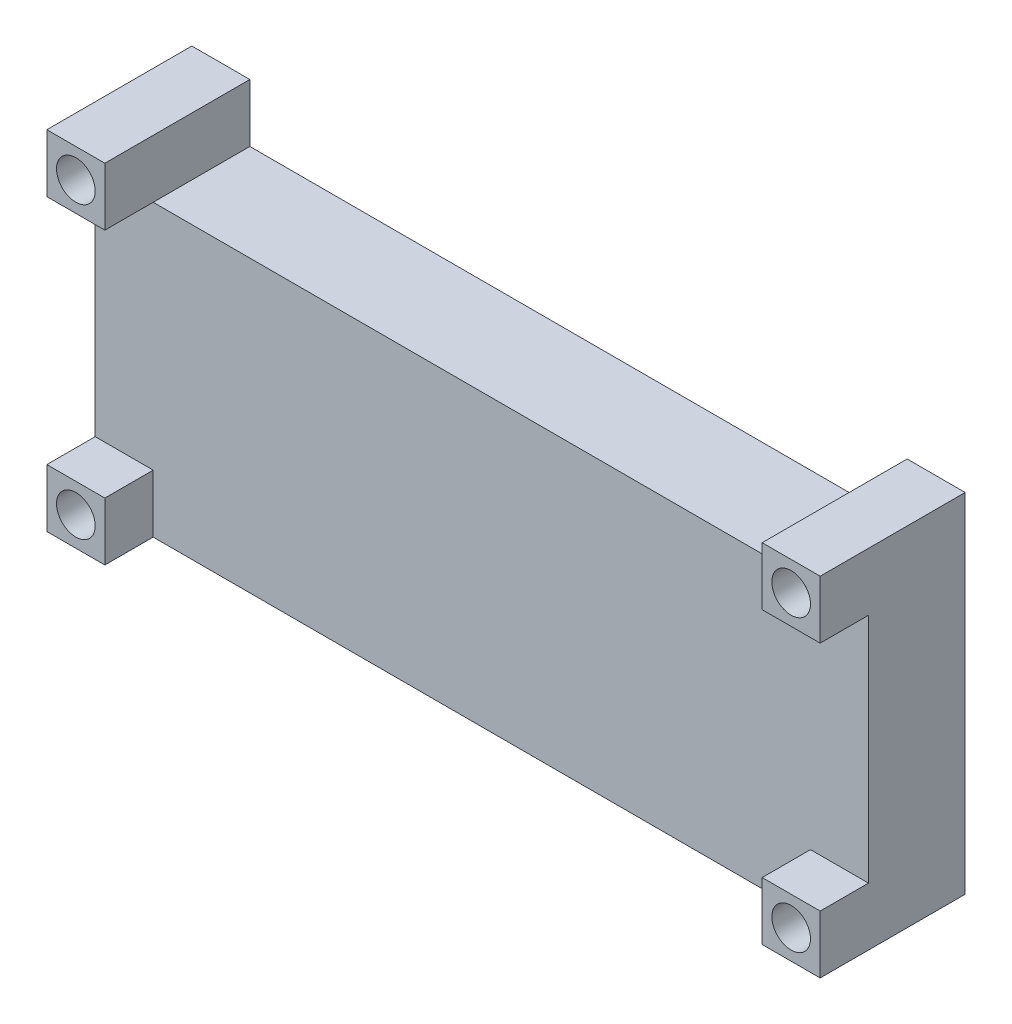
SolidWorks part; units mm, degrees
ref_plane "Front Plane" through (0, 0, 0) normal (0, 0, 1) x (1, 0, 0)
ref_plane "Top Plane" through (0, 0, 0) normal (0, 1, 0) x (1, 0, 0)
ref_plane "Right Plane" through (0, 0, 0) normal (1, 0, 0) x (0, 0, -1)
sketch "Sketch1" plane through (0, 0, 0) normal (0, 0, 1) x (1, 0, 0)
  line L0 (0, 36) -> (6, 36)
  line L1 (0, 0) -> (80, 0)
  line L2 (0, 0) -> (0, 36)
  line L4 (80, 0) -> (80, 36)
  line L5 (6, 36) -> (6, 30)
  line L6 (6, 30) -> (74, 30)
  line L7 (74, 30) -> (74, 36)
  line L8 (74, 36) -> (80, 36)
  point P9 (0, 0)
  point P10 (0, 0)
  point P11 (74, 34.5478)
  dimension "D1" = 36
  dimension "D2" = 6
  dimension "80" = 80
extrude "Boss-Extrude1" add sketch "Sketch1" along normal blind 10
sketch "Sketch2" plane through (0, 0, 10) normal (0, 0, 1) x (1, 0, 0)
  line L1 (0, 36) -> (6, 36)
  line L2 (0, 36) -> (0, 30)
  line L3 (0, 30) -> (6, 30)
  line L4 (6, 36) -> (6, 30)
  circle A0 centre (3, 33) radius 2
  point P8 (3, 36)
  point P9 (0, 33)
  dimension "D1" = 4
extrude "Boss-Extrude2" add sketch "Sketch2" along normal blind 5
extrude "Cut-Extrude1" cut sketch "Sketch2<2>" against normal through all contours A0
sketch "Sketch2<2>" plane through (0, 0, 10) normal (0, 0, 1) x (1, 0, 0) same geometry as "Sketch2"
pattern_linear "LPattern2" count 2 spacing 74 along (1, 0, 0) count 2 spacing 30 along (0, -1, 0) of "Cut-Extrude1", "Boss-Extrude2"
